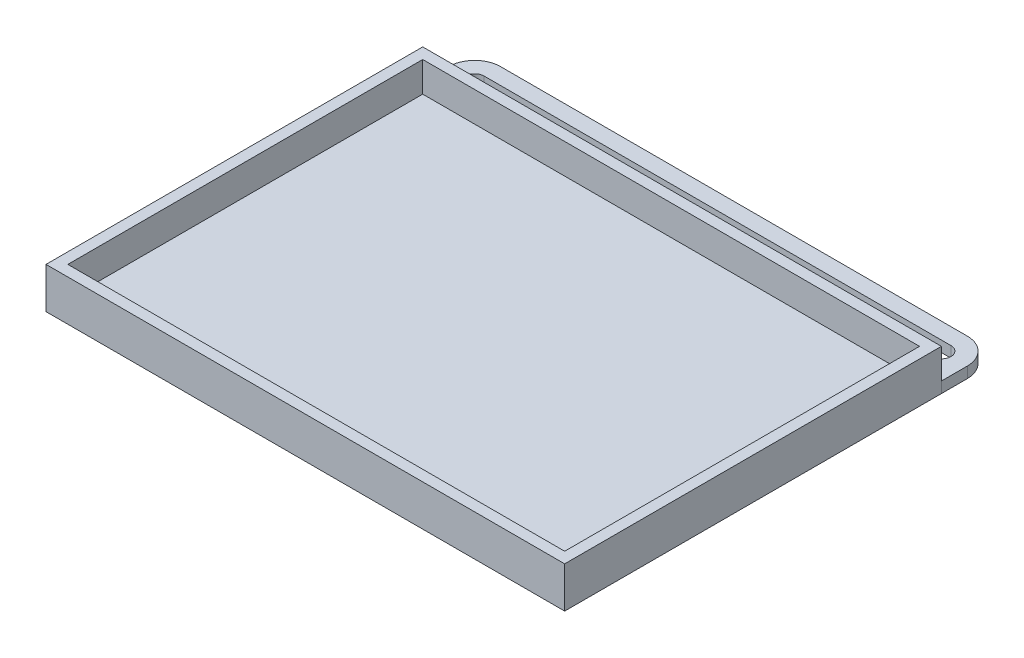
SolidWorks part; units mm, degrees
ref_plane "Alzado" through (0, 0, 0) normal (0, 0, 1) x (1, 0, 0)
ref_plane "Planta" through (0, 0, 0) normal (0, 1, 0) x (1, 0, 0)
ref_plane "Vista lateral" through (0, 0, 0) normal (1, 0, 0) x (0, 0, -1)
sketch "Croquis2" plane through (0, 0, 0) normal (0, 1, 0) x (1, 0, 0)
  line L0 (-3, -3) -> (-3, 68)
  line L1 (0, 0) -> (91, 0)
  line L2 (0, 0) -> (0, 65)
  line L3 (0, 65) -> (91, 65)
  line L4 (91, 0) -> (91, 65)
  line L5 (-3, 68) -> (94, 68)
  line L6 (94, -3) -> (94, 68)
  line L7 (-3, -3) -> (94, -3)
  dimension "D1" = 91
  dimension "D2" = 65
  dimension "D3" = 3
extrude "Saliente-Extruir1" add sketch "Croquis2" along normal blind 2 contours L1 L4 L3 L2 region at (45.5, 0, -32.5)
sketch "Croquis3" plane through (0, 2, 0) normal (0, 1, 0) x (1, 0, 0)
  line L0 (-2, 67) -> (-2, -2)
  line L1 (-2, -2) -> (93, -2)
  line L2 (93, -2) -> (93, 67)
  line L3 (93, 67) -> (-2, 67)
  line L4 (0, 0) -> (91, 0)
  line L5 (91, 0) -> (91, 65)
  line L6 (91, 65) -> (0, 65)
  line L7 (0, 65) -> (0, 0)
  line L8 (0, 0) -> (91, 0)
  line L9 (91, 0) -> (91, 65)
  line L10 (91, 65) -> (0, 65)
  line L11 (0, 65) -> (0, 0)
  dimension "D1" = 0
  dimension "D2" = 2
extrude "Saliente-Extruir2" add sketch "Croquis3" along normal blind 5.5
sketch "Croquis5" plane through (0, 2, 0) normal (0, 1, 0) x (1, 0, 0)
  line L0 (2.75, 71.75) -> (88.25, 71.75) construction
  line L1 (2.75, 73.5) -> (88.25, 73.5)
  line L2 (2.75, 70) -> (88.25, 70)
  line L6 (2.75, 76.5) -> (88.25, 76.5)
  line L7 (2.75, 67) -> (88.25, 67)
  line L9 (-2, 67) -> (-2, -2) construction
  line L10 (2.75, 67) -> (-2, 67)
  line L11 (91, 67) -> (0, 67)
  line L12 (-2, 67) -> (-2, 71.75)
  line L13 (88.25, 67) -> (93, 67)
  line L14 (93, -2) -> (93, 67) construction
  line L15 (93, 67) -> (93, 71.75)
  line L16 (0, 0) -> (91, 0) construction
  line L17 (93, 67) -> (-2, 67) construction
  arc A0 (2.75, 73.5) -> (2.75, 70) centre (2.75, 71.75) ccw
  arc A1 (88.25, 70) -> (88.25, 73.5) centre (88.25, 71.75) ccw
  arc A2 (88.25, 67) -> (88.25, 76.5) centre (88.25, 71.75) ccw
  arc A3 (2.75, 76.5) -> (2.75, 67) centre (2.75, 71.75) ccw
  point P2 (45.5, 71.75)
  point P28 (45.5, 0)
  point P29 (45.5, 67)
  dimension "D1" = 3.5
  dimension "D2" = 3
extrude "Saliente-Extruir3" add sketch "Croquis5" against normal blind 2 contours L6 A3 L7 A2 A1 L2 A0 L1 | A3 L11 | A2 L11 region at (45.5, 2, -75.5453) region at (-0.939, 2, -68.061) region at (91.939, 2, -68.061)
sketch "Croquis6" plane through (0, 2, 0) normal (0, 1, 0) x (1, 0, 0)
  line L1 (25.5, 0) -> (65.5, 0)
  line L2 (25.5, 0) -> (25.5, 1)
  line L3 (27.5, 3) -> (63.5, 3)
  line L4 (65.5, 0) -> (65.5, 1)
  line L6 (0, 0) -> (91, 0) construction
  line L7 (-2, -2) -> (93, -2) construction
  arc A0 (63.5, 3) -> (65.5, 1) centre (63.5, 1) cw
  arc A1 (25.5, 1) -> (27.5, 3) centre (27.5, 1) cw
  point P8 (45.5, -2)
  point P12 (65.5, 3)
  point P15 (25.5, 3)
  point P16 (45.5, 3)
  dimension "D3" = 2
  dimension "D1" = 40
  dimension "D2" = 3
extrude "Cortar-Extruir1" cut sketch "Croquis6" against normal through all
extrude "Saliente-Extruir4" add sketch "Croquis3<2>" along normal blind 5.5 and the other way up to surface (2 mm away) other way up to face at (45.5, 0, -13.8828)
sketch "Croquis3<2>" plane through (0, 2, 0) normal (0, 1, 0) x (1, 0, 0) same geometry as "Croquis3"
